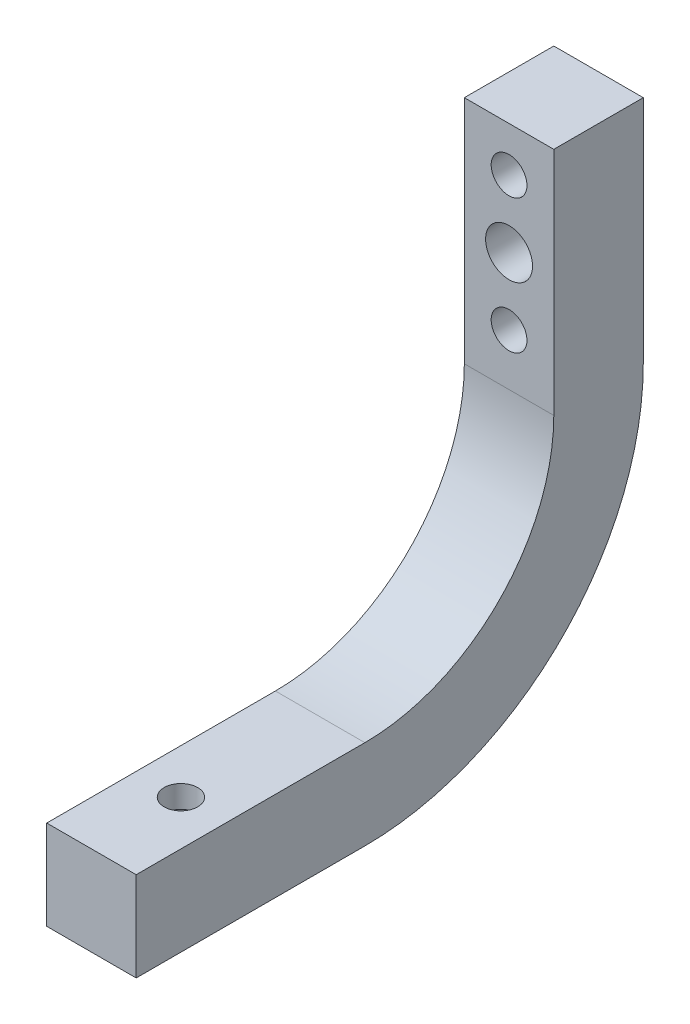
SolidWorks part; units mm, degrees
ref_plane "Front Plane" through (0, 0, 0) normal (0, 0, 1) x (1, 0, 0)
ref_plane "Top Plane" through (0, 0, 0) normal (0, 1, 0) x (1, 0, 0)
ref_plane "Right Plane" through (0, 0, 0) normal (1, 0, 0) x (0, 0, -1)
ref_axis "Z" through (0, 0, 60.732) along (0, 0, -1)
sketch "Sketch1" plane through (0, 0, 0) normal (1, 0, 0) x (0, 0, -1)
  line L0 (-8, 10) -> (0, 10)
  line L1 (0, 10) -> (0, -10.6067)
  line L2 (0, -18) -> (-17.5, -35.5) construction
  line L3 (-24.8933, -35.5) -> (-37.34, -35.5)
  line L4 (-37.34, -35.5) -> (-37.34, -27.5) construction
  line L5 (-37.34, -27.5) -> (-24.8933, -27.5)
  line L6 (-20.8137, -27.5) -> (-8, -14.6863) construction
  line L7 (-8, -10.6067) -> (-8, 10)
  line L8 (-14.4069, -21.0931) -> (-8.75, -26.75) construction
  line L9 (-24.8933, -27.5) -> (-20.8137, -27.5) construction
  line L10 (-37.34, -27.5) -> (-45.34, -27.5)
  line L11 (-37.34, -27.5) -> (-37.34, -35.5) construction
  line L12 (-37.34, -35.5) -> (-45.34, -35.5)
  line L13 (-45.34, -27.5) -> (-45.34, -35.5)
  line L14 (-8, -14.6863) -> (-8, -10.6067) construction
  line L15 (0, -10.6067) -> (0, -18) construction
  line L16 (-17.5, -35.5) -> (-24.8933, -35.5) construction
  arc A0 (-24.8933, -27.5) -> (-8, -10.6067) centre (-24.8933, -10.6067) ccw
  arc A1 (-24.8933, -35.5) -> (0, -10.6067) centre (-24.8933, -10.6067) ccw
  dimension "D2" = 37.34
  dimension "D3" = 35.5
  dimension "D4" = 10
  dimension "D5" = 135
  dimension "D6" = 17.5
  dimension "D7" = 8
  dimension "D8" = 12.4467
extrude "Boss-Extrude1" add sketch "Sketch1" along normal blind 4 and the other way blind 4
sketch "Sketch3" plane through (0, -27.5, 0) normal (0, 1, 0) x (1, 0, 0)
  line L0 (-4.4, 0) -> (4.4, 0) construction
  line L1 (0, -31.812) -> (0, 31.812) construction
  circle A0 centre (0, -37.34) radius 1.5
  dimension "D2" = 3
  dimension "D1" = 37.34
extrude "Cut-Extrude1" cut sketch "Sketch3" against normal through all
sketch "Sketch4" plane through (0, 0, 8) normal (0, 0, 1) x (1, 0, 0)
  line L0 (0, -6) -> (0, 6) construction
  circle A0 centre (0, 0) radius 2.1
  circle A1 centre (0, 6) radius 1.6
  circle A2 centre (0, -6) radius 1.6
  dimension "D1" = 4.2
  dimension "D3" = 3.2
  dimension "D2" = 12
extrude "Cut-Extrude2" cut sketch "Sketch4" against normal through all both and the other way through all
ref_axis "Axis1" through (0, -27.5, 37.34) along (0, 1, 0)
sketch "Sketch5" plane through (0, -35.5, 0) normal (0, -1, 0) x (1, 0, 0)
  circle A0 centre (0, 37.34) radius 2.275
  dimension "D1" = 4.55
extrude "Cut-Extrude3" cut sketch "Sketch5" against normal blind 6
sketch "Sketch6" plane through (0, -35.5, 0) normal (0, -1, 0) x (1, 0, 0)
  circle A0 centre (0, 37.34) radius 3.825
  dimension "D1" = 7.65
extrude "Cut-Extrude4" cut sketch "Sketch6" against normal blind 0.75
equation "\"rbracket-width\"=8"
equation "\"D1@Boss-Extrude1\"=\"rbracket-width\"/2"
equation "\"D2@Boss-Extrude1\"=\"rbracket-width\"/2"
equation "\"EyeCaptureRadius\"= ( \"EyeDiameter\" + \"EyeClearance\" ) / 2"
equation "\"rbracket_planetocenterline_dist\"= \"BasePlaneDistance\""
equation "\"D2@Sketch1\"=\"rbracket_planetocenterline_dist\""
equation "\"EyeDiameter\" = 35"
equation "\"BasePlaneDistance\" = \"EyeDiameter\"/2+19.84"
equation "\"EyeClearance\" = 2"
equation "\"D1@Sketch1\"=\"rbracket-width\""
equation "\"D3@Sketch1\"=(\"EyeDiameter\"+\"EyeClearance\"+\"EyeClearance\")/2 + \"L2Thickness\" + \"rbracket-width\""
equation "\"D4@Sketch1\"= 10"
equation "\"D6@Sketch1\"=\"EyeDiameter\"/2"
equation "\"D7@Sketch1\"=\"rbracket-width\""
equation "\"D1@Sketch3\"=\"BasePlaneDistance\""
equation "\"L2Thickness\" = 8"
equation "\"D8@Sketch1\"=\"rbracket_planetocenterline_dist\"/3"
equation "\"BearingFlangeOD\"= 7.5"
equation "\"BearingFlangeThickness\"= 0.75"
equation "\"BearingHousingID\"=4.5"
equation "\"BearingDepth\"= 6"
equation "\"D1@Sketch5\"=\"BearingHousingID\" + \"PrinterFilamentThickness\" * \"ApplyPrinterOffsets\" / 2"
equation "\"D1@Cut-Extrude3\"=\"BearingDepth\""
equation "\"D1@Sketch6\"=\"BearingFlangeOD\" + \"PrinterFilamentThickness\" * 1.5 * \"ApplyPrinterOffsets\""
equation "\"D1@Cut-Extrude4\"=\"BearingFlangeThickness\""
equation "\"PrinterFilamentThickness\"= 0.1"
equation "\"ApplyPrinterOffsets\"= 1"
